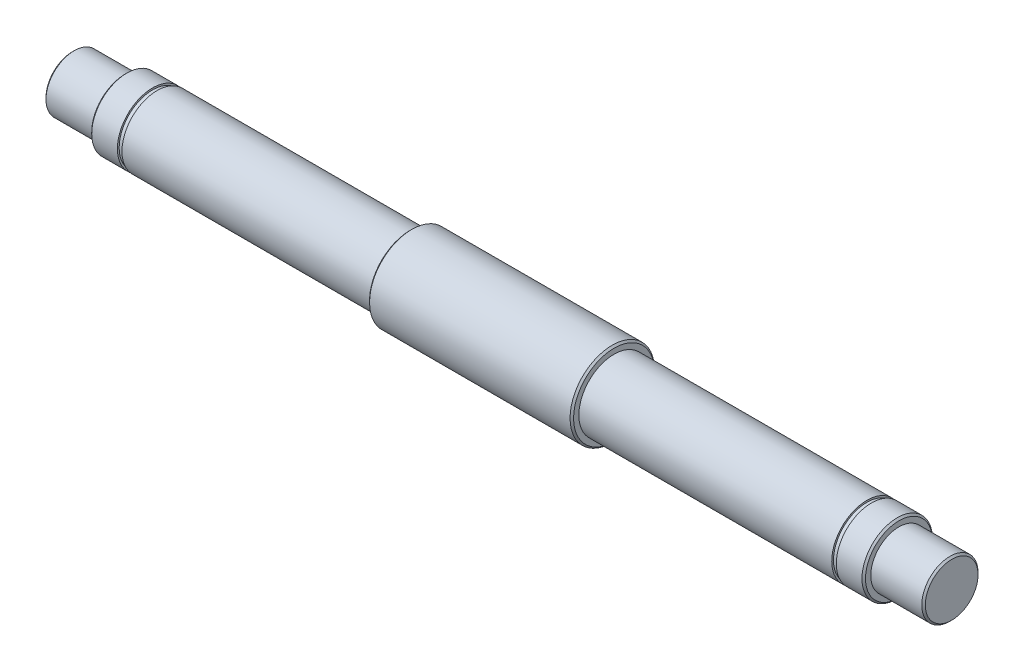
SolidWorks part; units mm, degrees
ref_plane "Front Plane" through (0, 0, 0) normal (0, 0, 1) x (1, 0, 0)
ref_plane "Top Plane" through (0, 0, 0) normal (0, 1, 0) x (1, 0, 0)
ref_plane "Right Plane" through (0, 0, 0) normal (1, 0, 0) x (0, 0, -1)
sketch "Sketch1" plane through (0, 0, 0) normal (0, 1, 0) x (1, 0, 0)
  line L0 (-125, 0) -> (125, 0) construction
  line L1 (-125, 0) -> (-125, 8)
  line L2 (-125, 8) -> (-110, 8)
  line L3 (-110, 8) -> (-110, 10)
  line L4 (0, 0) -> (0, 68.7304) construction
  line L5 (-110, 10) -> (-102.2, 10)
  line L6 (-29, 10) -> (-29, 12)
  line L7 (-29, 12) -> (29, 12)
  line L8 (-101, 12.5) -> (-101, -12.5) construction
  line L9 (-102.2, 10) -> (-102.2, 9.5)
  line L10 (-102.2, 9.5) -> (-100.9, 9.5)
  line L11 (-100.9, 9.5) -> (-100.9, 10)
  line L12 (-100.9, 10) -> (-29, 10)
  line L13 (100.9, 10) -> (29, 10)
  line L14 (100.9, 9.5) -> (100.9, 10)
  line L15 (102.2, 9.5) -> (100.9, 9.5)
  line L16 (102.2, 10) -> (102.2, 9.5)
  line L17 (29, 10) -> (29, 12)
  line L18 (110, 10) -> (102.2, 10)
  line L19 (110, 8) -> (110, 10)
  line L20 (125, 8) -> (110, 8)
  line L21 (125, 0) -> (125, 8)
  line L22 (-125, 0) -> (125, 0)
  point P19 (0, 12)
  point P27 (29, 11)
  dimension "D1" = 250
  dimension "D2" = 24
  dimension "D3" = 20
  dimension "D4" = 16
  dimension "D5" = 15
  dimension "D7" = 19
  dimension "D8" = 1.3
  dimension "D9" = 0.1
  dimension "D6" = 58
revolve "Revolve1" add sketch "Sketch1" angle 360 about L22
chamfer "Chamfer1" distance 0.5 angle 45 6 edges at (110, 0, 10) (125, 0, 8) (29, 0, 12) (-29, 0, 12) (-110, 0, 10) (-125, 0, 8)
equation "\"d_ext_rouleau\"= 90"
equation "\"epaisseur_rouleau\"=80"
equation "\"alesage-rouleau\"= 52"
equation "\"jeu_dent_rouleau\"= 2"
equation "\"profondeur_dent_rouleau\"=4"
equation "\"n_dent_roueau\"= 15"
equation "\"B_roulement_rouleau\"= 12"
equation "\"F_anneau_alesage_rouleau\"=1.85"
equation "\"G_anneau_alesage_rouleau\"=47.5"
equation "\"K_anneau_alesage_rouleau\"=3.75"
equation "\"d_vis_flasque_rouleau\"=5"
equation "\"h_matrice\"= 18"
equation "\"d_matrice\"= 220"
equation "\"d_granulat\"= 8"
equation "\"zone_vide_matrice\" = 48"
equation "\"d_alesage_matrice\"=20"
equation "\"a_clavette_alesage_matrice\"=6"
equation "\"D2@Sketch1\"=\"d_int_roulement_rouleau\" + 4"
equation "\"D1@Sketch1\"=\"d_matrice\"+30"
equation "\"g_anneau_arbre_rouleau\"=19"
equation "\"D7@Sketch1\"=\"g_anneau_arbre_rouleau\""
equation "\"f_anneau_arbre_rouleau\"=1.3"
equation "\"D8@Sketch1\"=\"f_anneau_arbre_rouleau\""
equation "\"k_anneau_arbre_rouleau\"=1.5"
equation "\"d_ext_roulement_rouleau\"= 42"
equation "\"d_int_roulement_rouleau\"= 20"
equation "\"L_arbre_arbre_rouleau\"=15"
equation "\"D5@Sketch1\"=\"L_arbre_arbre_rouleau\""
equation "\"D6@Sketch1\"=\"zone_vide_matrice\"+10"
